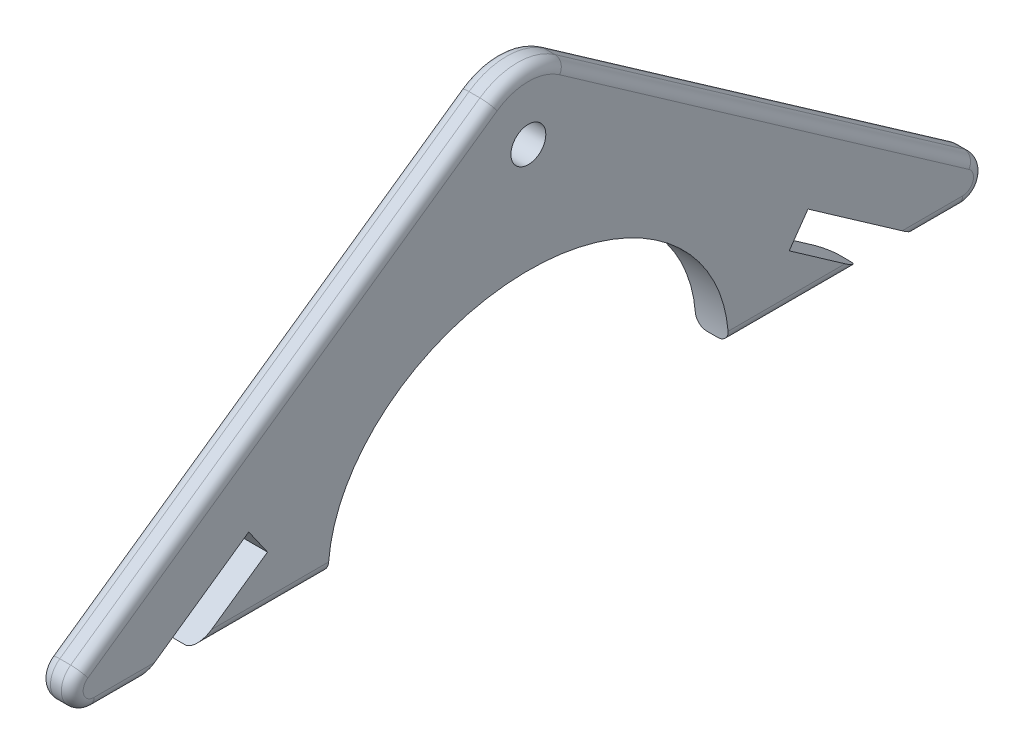
SolidWorks part; units mm, degrees
ref_plane "Front Plane" through (0, 0, 0) normal (0, 0, 1) x (1, 0, 0)
ref_plane "Top Plane" through (0, 0, 0) normal (0, 1, 0) x (1, 0, 0)
ref_plane "Right Plane" through (0, 0, 0) normal (1, 0, 0) x (0, 0, -1)
sketch "Sketch1" plane through (0, 0, 0) normal (1, 0, 0) x (0, 0, -1)
  line L0 (0, 0) -> (0, 9.7181) construction
  line L1 (0, 0) -> (-3.4415, 4.9149) construction
  line L2 (-3.4415, 4.9149) -> (-40.9683, -21.3617)
  line L3 (0, 0) -> (0, -25) construction
  line L4 (-18.3534, -25) -> (-30.4734, -25)
  line L5 (-35.7037, -25) -> (-25.6409, -17.9539)
  line L6 (-35.7037, -25) -> (-39.8212, -25)
  line L7 (-25.6409, -17.9539) -> (-23.9201, -20.4114)
  line L8 (-30.4734, -25) -> (-23.9201, -20.4114)
  line L9 (-34.1137, -16.5621) -> (-30.6723, -21.477) construction
  line L11 (30.4734, -25) -> (23.9201, -20.4114)
  line L12 (0, -25) -> (0, -7) construction
  line L15 (25.6409, -17.9539) -> (23.9201, -20.4114)
  line L16 (35.7037, -25) -> (39.8212, -25)
  line L17 (35.7037, -25) -> (25.6409, -17.9539)
  line L18 (18.3534, -25) -> (30.4734, -25)
  line L19 (3.4415, 4.9149) -> (40.9683, -21.3617)
  line L20 (-46.1644, -25) -> (-18.3534, -25) construction
  arc A0 (3.4415, 4.9149) -> (-3.4415, 4.9149) centre (0, 0) ccw
  circle A1 centre (0, 0) radius 1.6
  arc A2 (40.9683, -21.3617) -> (39.8212, -25) centre (39.8212, -23) cw
  arc A3 (-40.9683, -21.3617) -> (-39.8212, -25) centre (-39.8212, -23) ccw
  ellipse E0 centre (0, -25) end of major axis (-18.3534, -25) minor radius 15 (18.3534, -25) -> (-18.3534, -25) ccw
  point P24 (46.1644, -25)
  point P25 (46.1644, -25)
  dimension "D1" = 6
  dimension "D9" = 3.2
  dimension "D10" = 2
  dimension "D2" = 25
  dimension "D3" = 35
  dimension "D4" = 6
  dimension "D6" = 3
  dimension "D7" = 8
extrude "Boss-Extrude1" add sketch "Sketch1" along normal blind 3
fillet "Fillet1" radius 1 18 edges at (0, -25, -37.7624) (0, -8.2234, -22.2049) (0, 6, 0) (0, -25, 37.7624) (3, -25, -37.7624) (3, -8.2234, -22.2049) (3, 6, 0) (3, -25, 37.7624) (0, -25, -24.4134) (3, -25, -24.4134) (0, -25, 24.4134) (3, -25, 24.4134) (0, -8.2234, 22.2049) (3, -8.2234, 22.2049) (0, -23.6014, -41.7286) (0, -23.6014, 41.7286) (3, -23.6014, -41.7286) (3, -23.6014, 41.7286)
